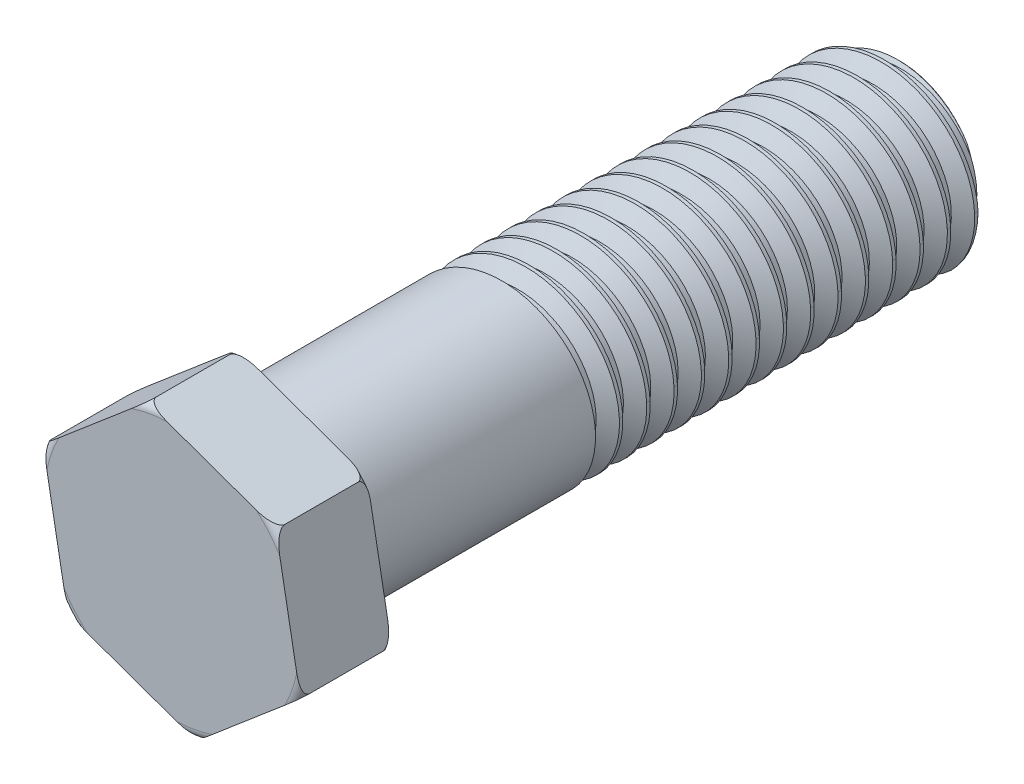
SolidWorks part; units mm, degrees
ref_plane "Ön Düzlem" through (0, 0, 0) normal (0, 0, 1) x (1, 0, 0)
ref_plane "Üst Düzlem" through (0, 0, 0) normal (0, 1, 0) x (1, 0, 0)
ref_plane "Sağ Düzlem" through (0, 0, 0) normal (1, 0, 0) x (0, 0, -1)
sketch "Çizim1" plane through (0, 0, 0) normal (0, 0, 1) x (1, 0, 0)
  circle A0 centre (0, 0) radius 10
extrude "Yükseklik-Ekstrüzyon1" add sketch "Çizim1" along normal blind 70
sketch "Çizim2" plane through (0, 0, 70) normal (0, 0, 1) x (1, 0, 0)
  circle A0 centre (0, 0) radius 15
extrude "Yükseklik-Ekstrüzyon2" add sketch "Çizim2" along normal blind 10
fillet "Radyus2" radius 1 2 edges at (15, 0, 80) (15, 0, 70)
chamfer "Pah1" distance 1.5 angle 45 1 edges at (10, 0, 0)
thread "Diş1" pitch 3 method cut profile "Diş Profili2" start angle 0, offset 25, length 65, pitch 3, diameter 20
ref_plane "Düzlem2" through (-10, 0, 45) normal (0, -1, 0) x (-1, 0, 0)
sketch "Diş Profili2" plane through (-10, 0, 45) normal (0, -1, 0) x (-1, 0, 0)
  line L0 (0, 0) -> (0, 3) construction
  line L11 (0, 0) -> (0, 2.625)
  line L12 (0, 2.625) -> (-1.6238, 1.6875)
  line L13 (-1.6238, 1.6875) -> (-1.6238, 0.9375)
  line L15 (-1.6238, 0.9375) -> (0, 0)
  line L17 (-1.6238, 1.3125) -> (0, 1.3125) construction
  point P2 (0, 0)
  dimension "Pitch" = 3
  dimension "Profile_Angle" = 60
  dimension "Profile_Land" = 0.75
  dimension "Profile_Height" = 1.6238
sketch "Çizim8" plane through (0, 0, 80) normal (0, 0, 1) x (1, 0, 0)
  line L6 (11.4319, 9.7114) -> (-2.6944, 14.756)
  line L7 (-2.6944, 14.756) -> (-14.1263, 5.0446)
  line L8 (-14.1263, 5.0446) -> (-11.4319, -9.7114)
  line L9 (-11.4319, -9.7114) -> (2.6944, -14.756)
  line L10 (2.6944, -14.756) -> (14.1263, -5.0446)
  line L11 (14.1263, -5.0446) -> (11.4319, 9.7114)
  circle A0 centre (0, 0) radius 15 construction
extrude "Kes-Ekstrüzyon1" cut sketch "Çizim8" against normal blind 10 flip side to cut
